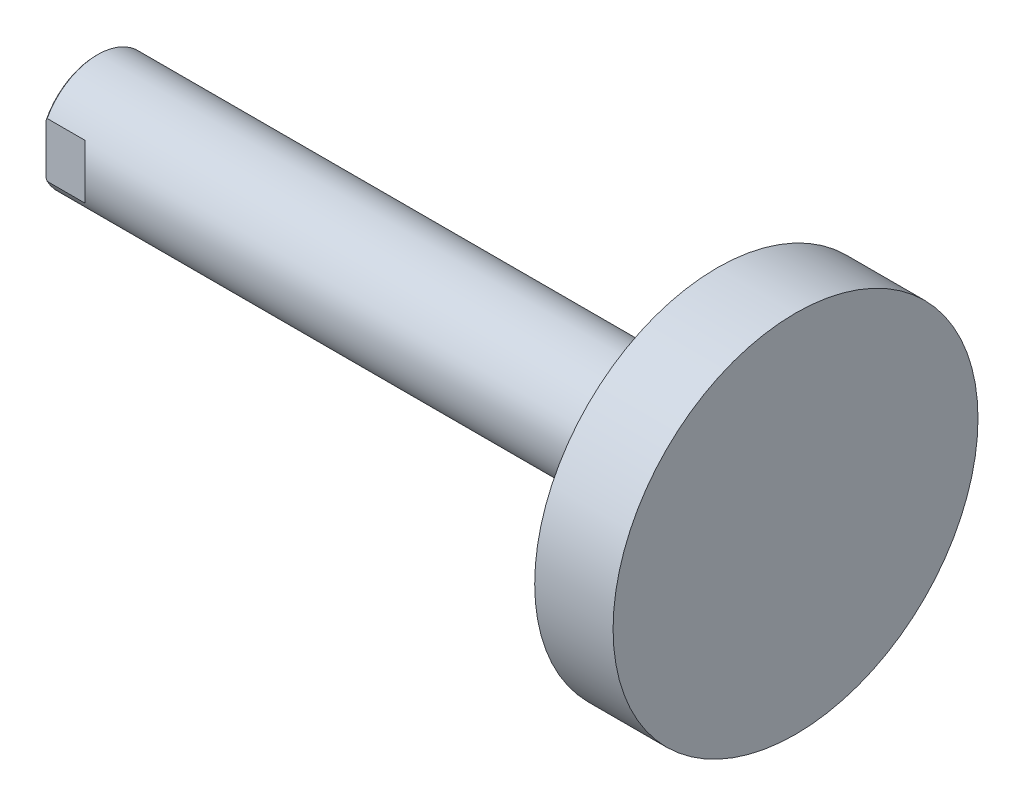
SolidWorks part; units mm, degrees
ref_plane "前视基准面" through (0, 0, 0) normal (0, 0, 1) x (1, 0, 0)
ref_plane "上视基准面" through (0, 0, 0) normal (0, 1, 0) x (1, 0, 0)
ref_plane "右视基准面" through (0, 0, 0) normal (1, 0, 0) x (0, 0, -1)
sketch "草图1" plane through (0, 0, 0) normal (0, 0, 1) x (1, 0, 0)
  line L0 (-10, 0) -> (-10, 12.25)
  line L1 (-10, 12.25) -> (-9.75, 12.5)
  line L2 (-9.75, 12.5) -> (0, 12.5)
  line L3 (0, 12.5) -> (0, 0)
  line L4 (0, 0) -> (-10, 0)
  line L5 (0, 0) -> (-10, 0) construction
revolve "旋转1" add sketch "草图1" angle 360 about L5 reverse direction yes
sketch "草图2" plane through (0, 0, 0) normal (0, 0, 1) x (1, 0, 0)
  line L0 (0, 0) -> (0, 12.5)
  line L1 (0, 12.5) -> (125.4, 12.5)
  line L2 (125.4, 12.5) -> (125.4, 39.8)
  line L3 (125.4, 39.8) -> (142.5, 39.8)
  line L4 (142.5, 39.8) -> (142.5, 0)
  line L5 (142.5, 0) -> (0, 0)
  line L6 (142.5, 0) -> (0, 0) construction
revolve "旋转2" add sketch "草图2" angle 360 about L6 reverse direction yes
sketch "草图3" plane through (0, 0, 0) normal (0, 1, 0) x (1, 0, 0)
  line L0 (-20, -16) -> (3.5, -16)
  line L1 (3.5, -16) -> (-1.5, -11)
  line L2 (-1.5, -11) -> (-10, -11)
  line L3 (-10, -11) -> (-10, 11)
  line L4 (-10, 11) -> (-1.5, 11)
  line L5 (-1.5, 11) -> (3.5, 16)
  line L6 (3.5, 16) -> (-20, 16)
  line L7 (-20, 16) -> (-20, -16)
extrude "切除-拉伸1" cut sketch "草图3" along normal blind 22 and the other way blind 22
hole_wizard "孔1" positions "草图5" profile "草图4" legacy
sketch "草图5" plane through (-10, 0, 0) normal (-1, 0, 0) x (0, 0, 1)
  point P0 (0, 0)
sketch "草图4" plane through (-10, 0, 0) normal (0, 1, 0) x (0, 0, 1)
  line L0 (0, 0) -> (0, 27.9938)
  line L1 (0, 27.9938) -> (6.9175, 24)
  line L2 (6.9175, 24) -> (6.9175, 1.0825)
  line L3 (6.9175, 1.0825) -> (8, 0)
  line L4 (8, 0) -> (0, 0)
  line L5 (0, -14.3089) -> (0, 102.4216) construction
  line L6 (0, 27.9938) -> (-6.9175, 24) construction
  line L7 (-6.9175, 1.0825) -> (-8, 0) construction
  dimension "直径" = 13.835
  dimension "深度" = 24
  dimension "锥坑直径" = 16
  dimension "锥坑角度" = 90
  dimension "导头角度" = 120
cosmetic thread "装饰螺纹线1" parameters "D1"=20, "D2"=16
ref_plane "基准面1" through (0, 0, 0) normal (1, 0, 0) x (0, 0, -1)
ref_plane "rod XY" through (0, 0, 0) normal (1, 0, 0) x (0, 0, -1)
ref_plane "rod XZ" through (0, 0, 0) normal (0, -1, 0) x (-1, 0, 0)
ref_plane "rod YZ" through (0, 0, 0) normal (0, 0, -1) x (-1, 0, 0)
ref_axis "rod X" through (0, 0, 80.9) along (0, 0, -1)
ref_axis "rod Y" through (0, -50, 0) along (0, 1, 0)
ref_axis "rod Z" through (80.9, 0, 0) along (-1, 0, 0)
sketch3d "rod"
  point P0 (0, 0, 0)
